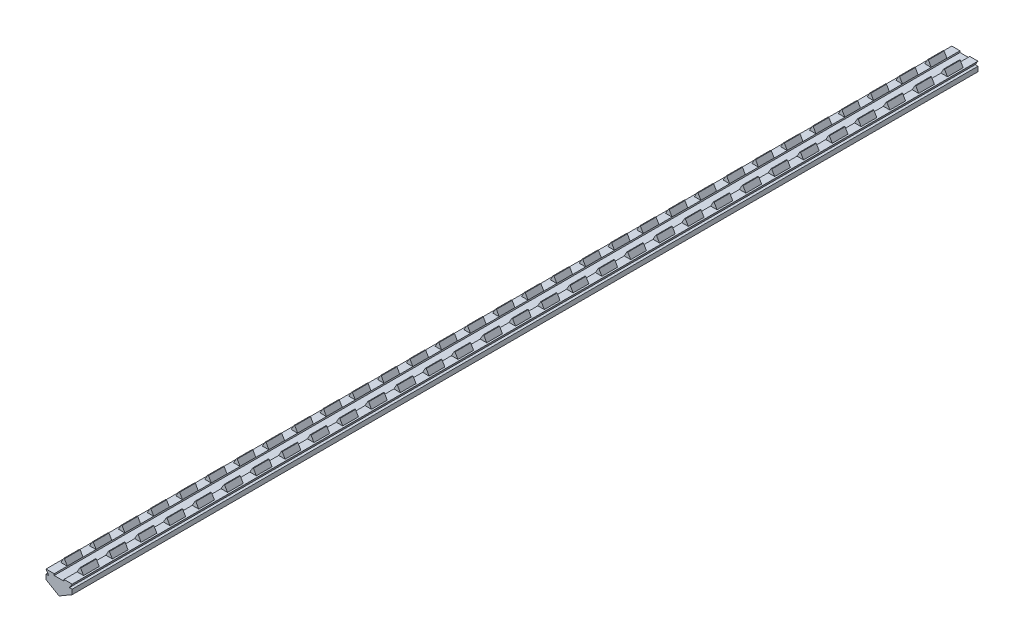
SolidWorks part; units mm, degrees
material "6061-T4 (SS)"
ref_plane "Front Plane" through (0, 0, 0) normal (0, 0, 1) x (1, 0, 0)
ref_plane "Top Plane" through (0, 0, 0) normal (0, 1, 0) x (1, 0, 0)
ref_plane "Right Plane" through (0, 0, 0) normal (1, 0, 0) x (0, 0, -1)
sketch "Sketch1" plane through (0, 0, 0) normal (0, 0, 1) x (1, 0, 0)
  line L20 (0, 0) -> (-6, 3.4991)
  line L21 (-6, 3.4991) -> (-6, 5.6991)
  line L22 (-6, 5.6991) -> (-4.75, 5.6991)
  line L23 (-4.75, 5.6991) -> (-6, 7.6991)
  line L24 (-6, 7.6991) -> (-5.2, 7.6991)
  line L25 (-5.2, 7.6991) -> (-3.8716, 10)
  line L26 (-3.8716, 10) -> (-3.5416, 10)
  line L27 (-3.5416, 10) -> (-2.2425, 7.75)
  line L28 (-2.2425, 7.75) -> (-2.2425, 7)
  line L29 (-2.2425, 7) -> (2.2425, 7)
  line L30 (0, 0) -> (0, 8.0051) construction
  line L31 (2.2425, 7.75) -> (2.2425, 7)
  line L32 (3.5416, 10) -> (2.2425, 7.75)
  line L33 (3.8716, 10) -> (3.5416, 10)
  line L34 (5.2, 7.6991) -> (3.8716, 10)
  line L35 (6, 7.6991) -> (5.2, 7.6991)
  line L36 (4.75, 5.6991) -> (6, 7.6991)
  line L37 (6, 5.6991) -> (4.75, 5.6991)
  line L38 (6, 3.4991) -> (6, 5.6991)
  line L39 (0, 0) -> (6, 3.4991)
  point P35 (0, 7)
  dimension "D14" = 2.2
  dimension "D15" = 60
  dimension "D16" = 1.25
  dimension "D17" = 0.8
  dimension "D18" = 0.75
  dimension "D19" = 10
  dimension "D20" = 7
  dimension "D21" = 12
  dimension "D22" = 0.33
  dimension "D23" = 119.5
  dimension "D24" = 2
extrude "Boss-Extrude1" add sketch "Sketch1" along normal mid plane 415
sketch "Sketch2" plane through (0, 0, 0) normal (1, 0, 0) x (0, 0, -1)
  line L0 (-194.3063, 13.6991) -> (-188.3063, 13.6991)
  line L1 (-207.5, 7.6991) -> (-201.5, 7.6991)
  line L2 (-207.5, 7.6991) -> (-207.5, 13.6991)
  line L3 (-207.5, 13.6991) -> (-201.5, 13.6991)
  line L4 (-201.5, 7.6991) -> (-201.5, 13.6991)
  line L5 (-207.5, 7.6991) -> (-201.5, 13.6991) construction
  line L6 (-207.5, 13.6991) -> (-201.5, 7.6991) construction
  line L7 (-194.3063, 7.6991) -> (-194.3063, 13.6991)
  line L8 (-194.3063, 7.6991) -> (-188.3063, 7.6991)
  line L9 (-188.3063, 7.6991) -> (-188.3063, 13.6991)
  line L10 (-181.1127, 13.6991) -> (-175.1127, 13.6991)
  line L11 (-181.1127, 7.6991) -> (-181.1127, 13.6991)
  line L12 (-181.1127, 7.6991) -> (-175.1127, 7.6991)
  line L13 (-175.1127, 7.6991) -> (-175.1127, 13.6991)
  line L14 (-167.919, 13.6991) -> (-161.919, 13.6991)
  line L15 (-167.919, 7.6991) -> (-167.919, 13.6991)
  line L16 (-167.919, 7.6991) -> (-161.919, 7.6991)
  line L17 (-161.919, 7.6991) -> (-161.919, 13.6991)
  line L18 (-154.7253, 13.6991) -> (-148.7253, 13.6991)
  line L19 (-154.7253, 7.6991) -> (-154.7253, 13.6991)
  line L20 (-154.7253, 7.6991) -> (-148.7253, 7.6991)
  line L21 (-148.7253, 7.6991) -> (-148.7253, 13.6991)
  line L22 (-141.5316, 13.6991) -> (-135.5316, 13.6991)
  line L23 (-141.5316, 7.6991) -> (-141.5316, 13.6991)
  line L24 (-141.5316, 7.6991) -> (-135.5316, 7.6991)
  line L25 (-135.5316, 7.6991) -> (-135.5316, 13.6991)
  line L26 (-128.338, 13.6991) -> (-122.338, 13.6991)
  line L27 (-128.338, 7.6991) -> (-128.338, 13.6991)
  line L28 (-128.338, 7.6991) -> (-122.338, 7.6991)
  line L29 (-122.338, 7.6991) -> (-122.338, 13.6991)
  line L30 (-115.1443, 13.6991) -> (-109.1443, 13.6991)
  line L31 (-115.1443, 7.6991) -> (-115.1443, 13.6991)
  line L32 (-115.1443, 7.6991) -> (-109.1443, 7.6991)
  line L33 (-109.1443, 7.6991) -> (-109.1443, 13.6991)
  line L34 (-101.9506, 13.6991) -> (-95.9506, 13.6991)
  line L35 (-101.9506, 7.6991) -> (-101.9506, 13.6991)
  line L36 (-101.9506, 7.6991) -> (-95.9506, 7.6991)
  line L37 (-95.9506, 7.6991) -> (-95.9506, 13.6991)
  line L38 (-88.7569, 13.6991) -> (-82.7569, 13.6991)
  line L39 (-88.7569, 7.6991) -> (-88.7569, 13.6991)
  line L40 (-88.7569, 7.6991) -> (-82.7569, 7.6991)
  line L41 (-82.7569, 7.6991) -> (-82.7569, 13.6991)
  line L42 (-75.5633, 13.6991) -> (-69.5633, 13.6991)
  line L43 (-75.5633, 7.6991) -> (-75.5633, 13.6991)
  line L44 (-75.5633, 7.6991) -> (-69.5633, 7.6991)
  line L45 (-69.5633, 7.6991) -> (-69.5633, 13.6991)
  line L46 (-62.3696, 13.6991) -> (-56.3696, 13.6991)
  line L47 (-62.3696, 7.6991) -> (-62.3696, 13.6991)
  line L48 (-62.3696, 7.6991) -> (-56.3696, 7.6991)
  line L49 (-56.3696, 7.6991) -> (-56.3696, 13.6991)
  line L50 (-49.1759, 13.6991) -> (-43.1759, 13.6991)
  line L51 (-49.1759, 7.6991) -> (-49.1759, 13.6991)
  line L52 (-49.1759, 7.6991) -> (-43.1759, 7.6991)
  line L53 (-43.1759, 7.6991) -> (-43.1759, 13.6991)
  line L54 (-35.9823, 13.6991) -> (-29.9823, 13.6991)
  line L55 (-35.9823, 7.6991) -> (-35.9823, 13.6991)
  line L56 (-35.9823, 7.6991) -> (-29.9823, 7.6991)
  line L57 (-29.9823, 7.6991) -> (-29.9823, 13.6991)
  line L58 (-22.7886, 13.6991) -> (-16.7886, 13.6991)
  line L59 (-22.7886, 7.6991) -> (-22.7886, 13.6991)
  line L60 (-22.7886, 7.6991) -> (-16.7886, 7.6991)
  line L61 (-16.7886, 7.6991) -> (-16.7886, 13.6991)
  line L62 (-9.5949, 13.6991) -> (-3.5949, 13.6991)
  line L63 (-9.5949, 7.6991) -> (-9.5949, 13.6991)
  line L64 (-9.5949, 7.6991) -> (-3.5949, 7.6991)
  line L65 (-3.5949, 7.6991) -> (-3.5949, 13.6991)
  line L66 (3.5988, 13.6991) -> (9.5988, 13.6991)
  line L67 (3.5988, 7.6991) -> (3.5988, 13.6991)
  line L68 (3.5988, 7.6991) -> (9.5988, 7.6991)
  line L69 (9.5988, 7.6991) -> (9.5988, 13.6991)
  line L70 (16.7924, 13.6991) -> (22.7924, 13.6991)
  line L71 (16.7924, 7.6991) -> (16.7924, 13.6991)
  line L72 (16.7924, 7.6991) -> (22.7924, 7.6991)
  line L73 (22.7924, 7.6991) -> (22.7924, 13.6991)
  line L74 (29.9861, 13.6991) -> (35.9861, 13.6991)
  line L75 (29.9861, 7.6991) -> (29.9861, 13.6991)
  line L76 (29.9861, 7.6991) -> (35.9861, 7.6991)
  line L77 (35.9861, 7.6991) -> (35.9861, 13.6991)
  line L78 (43.1798, 13.6991) -> (49.1798, 13.6991)
  line L79 (43.1798, 7.6991) -> (43.1798, 13.6991)
  line L80 (43.1798, 7.6991) -> (49.1798, 7.6991)
  line L81 (49.1798, 7.6991) -> (49.1798, 13.6991)
  line L82 (56.3735, 13.6991) -> (62.3735, 13.6991)
  line L83 (56.3735, 7.6991) -> (56.3735, 13.6991)
  line L84 (56.3735, 7.6991) -> (62.3735, 7.6991)
  line L85 (62.3735, 7.6991) -> (62.3735, 13.6991)
  line L86 (69.5671, 13.6991) -> (75.5671, 13.6991)
  line L87 (69.5671, 7.6991) -> (69.5671, 13.6991)
  line L88 (69.5671, 7.6991) -> (75.5671, 7.6991)
  line L89 (75.5671, 7.6991) -> (75.5671, 13.6991)
  line L90 (82.7608, 13.6991) -> (88.7608, 13.6991)
  line L91 (82.7608, 7.6991) -> (82.7608, 13.6991)
  line L92 (82.7608, 7.6991) -> (88.7608, 7.6991)
  line L93 (88.7608, 7.6991) -> (88.7608, 13.6991)
  line L94 (95.9545, 13.6991) -> (101.9545, 13.6991)
  line L95 (95.9545, 7.6991) -> (95.9545, 13.6991)
  line L96 (95.9545, 7.6991) -> (101.9545, 7.6991)
  line L97 (101.9545, 7.6991) -> (101.9545, 13.6991)
  line L98 (109.1481, 13.6991) -> (115.1481, 13.6991)
  line L99 (109.1481, 7.6991) -> (109.1481, 13.6991)
  line L100 (109.1481, 7.6991) -> (115.1481, 7.6991)
  line L101 (115.1481, 7.6991) -> (115.1481, 13.6991)
  line L102 (122.3418, 13.6991) -> (128.3418, 13.6991)
  line L103 (122.3418, 7.6991) -> (122.3418, 13.6991)
  line L104 (122.3418, 7.6991) -> (128.3418, 7.6991)
  line L105 (128.3418, 7.6991) -> (128.3418, 13.6991)
  line L106 (135.5355, 13.6991) -> (141.5355, 13.6991)
  line L107 (135.5355, 7.6991) -> (135.5355, 13.6991)
  line L108 (135.5355, 7.6991) -> (141.5355, 7.6991)
  line L109 (141.5355, 7.6991) -> (141.5355, 13.6991)
  line L110 (148.7292, 13.6991) -> (154.7292, 13.6991)
  line L111 (148.7292, 7.6991) -> (148.7292, 13.6991)
  line L112 (148.7292, 7.6991) -> (154.7292, 7.6991)
  line L113 (154.7292, 7.6991) -> (154.7292, 13.6991)
  line L114 (161.9228, 13.6991) -> (167.9228, 13.6991)
  line L115 (161.9228, 7.6991) -> (161.9228, 13.6991)
  line L116 (161.9228, 7.6991) -> (167.9228, 7.6991)
  line L117 (167.9228, 7.6991) -> (167.9228, 13.6991)
  line L118 (175.1165, 13.6991) -> (181.1165, 13.6991)
  line L119 (175.1165, 7.6991) -> (175.1165, 13.6991)
  line L120 (175.1165, 7.6991) -> (181.1165, 7.6991)
  line L121 (181.1165, 7.6991) -> (181.1165, 13.6991)
  line L122 (188.3102, 13.6991) -> (194.3102, 13.6991)
  line L123 (188.3102, 7.6991) -> (188.3102, 13.6991)
  line L124 (188.3102, 7.6991) -> (194.3102, 7.6991)
  line L125 (194.3102, 7.6991) -> (194.3102, 13.6991)
  line L126 (201.5039, 13.6991) -> (207.5039, 13.6991)
  line L127 (201.5039, 7.6991) -> (201.5039, 13.6991)
  line L128 (201.5039, 7.6991) -> (207.5039, 7.6991)
  line L129 (207.5039, 7.6991) -> (207.5039, 13.6991)
  point P4 (-204.5, 10.6991)
  dimension "D1" = 6
  dimension "D2" = 6
  dimension "D3" = 32
extrude "Cut-Extrude1" cut sketch "Sketch2" against normal through all both and the other way through all
